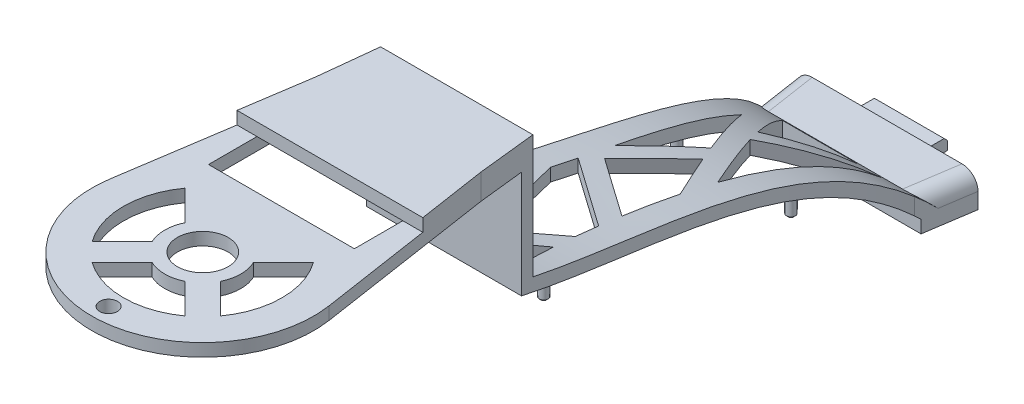
SolidWorks part; units mm, degrees
ref_plane "정면" through (0, 0, 0) normal (0, 0, 1) x (1, 0, 0)
ref_plane "윗면" through (0, 0, 0) normal (0, 1, 0) x (1, 0, 0)
ref_plane "우측면" through (0, 0, 0) normal (1, 0, 0) x (0, 0, -1)
sketch "스케치1" plane through (0, 0, 0) normal (1, 0, 0) x (0, 0, -1)
  line L1 (0, 0) -> (117.6994, 0)
  line L2 (0, 0) -> (0, 39)
  line L3 (0, 39) -> (125.5, 39)
  line L4 (125.5, 0) -> (125.5, 39)
  line L5 (120.5, 0) -> (95.5, 26.9) construction
  line L6 (95.5, 26.9) -> (48.49, 6.9) construction
  line L7 (48.49, 6.9) -> (20.28, 36.9) construction
  line L8 (20.28, 36.9) -> (20.28, 56.9) construction
  line L9 (55.6431, 37) -> (55.6431, -2)
  line L10 (0, -3.1) -> (125.5, -3.1) construction
  line L11 (0, -2) -> (125.5, -2)
  line L12 (0, 37) -> (55.6431, 37)
  line L13 (57.6431, 39) -> (57.6431, -2)
  line L14 (125.5, 0) -> (125.5, -2)
  line L15 (117.6994, 0) -> (117.6994, -2)
  line L16 (120.5, 0) -> (125.5, 0)
  line L17 (0, 0) -> (125.5, 0) construction
  line L18 (55.6431, 39) -> (55.6431, -2) construction
  line L19 (57.6431, 37) -> (125.5, 37)
  line L20 (0, 37) -> (125.5, 37) construction
  spline S0 degree 4 poles (120.5, 0) (95.5, 26.9) (48.49, 6.9) (20.28, 36.9) (20.28, 56.9) knots 0 0 0 0 0 1 1 1 1 1
  spline S1 degree 1 poles (119.035, -1.3615) (18.28, 56.9) knots 0 0 1 1 construction
  spline S2 degree 3 poles (119.035, -1.3615) (118.7108, -1.0127) (118.1523, -0.4358) (117.1322, 0.5491) (115.3881, 2.1024) (112.6944, 4.1207) (109.1843, 6.2121) (104.2498, 8.5701) (97.6622, 10.8405) (86.5016, 13.5333) (71.9342, 16.0164) (55.0254, 19.8159) (40.0095, 25.8104) (30.0498, 33.0505) (24.1324, 39.9432) (20.8302, 45.5049) (19.1097, 50.2945) (18.4017, 54.1131) (18.28, 55.9643) (18.28, 56.9) knots 0 0 0 0 0.010398 0.017329 0.03125 0.0625 0.09375 0.125 0.1875 0.25 0.375 0.5 0.625 0.75 0.8125 0.875 0.9375 0.96875 1 1 1 1 only from (117.6994, 0) to (18.28, 56.9)
  dimension "D1" = 125.5
  dimension "D2" = 39
  dimension "D4" = 5
  dimension "D5" = 30
  dimension "D6" = 10
  dimension "D7" = 40
  dimension "D8" = 20
  dimension "D9" = 30
  dimension "D10" = 47.01
  dimension "D11" = 28.21
  dimension "D12" = 3.1
  dimension "D13" = 2
  dimension "D14" = 2
  dimension "D15" = 2
  dimension "D16" = 2
extrude "보스-돌출3" add sketch "스케치1" along normal blind 35 contours L12 S2 L3 L2 | S2 L12 S0 L3 | S0 L13 L3 L12 L9 | S2 L13 S0 L9 | S2 L15 L11 L14 L16 S0 L13
sketch "스케치3" plane through (0, 0, -125.5) normal (0, 0, -1) x (-1, 0, 0)
  line L0 (0, 0) -> (0, 21.5828) construction
  line L1 (-35, -2) -> (0, -2)
  line L2 (-35, -2) -> (-35, 3)
  line L3 (-35, 3) -> (0, 3)
  line L4 (0, -2) -> (0, 3)
  dimension "D1" = 5
extrude "보스-돌출4" add sketch "스케치3" against normal up to next
sketch "스케치4" plane through (0, 39, 0) normal (0, 1, 0) x (1, 0, 0)
  line L1 (6, 50) -> (29, 50)
  line L2 (6, 50) -> (6, 30)
  line L3 (6, 30) -> (29, 30)
  line L4 (29, 50) -> (29, 30)
  line L5 (0, 0) -> (0, 57.6431) construction
  line L6 (35, 0) -> (35, 57.6431) construction
  line L8 (35, 0) -> (0, 0) construction
  dimension "D1" = 30
  dimension "D2" = 6
  dimension "D3" = 6
  dimension "D4" = 20
extrude "컷-돌출1" cut sketch "스케치4" against normal up to next
sketch "스케치6" plane through (0, 39, 0) normal (0, 1, 0) x (1, 0, 0)
  line L0 (35, 0) -> (35, 57.6431) construction
  line L1 (0, 57.6431) -> (35, 57.6431)
  line L2 (0, 57.6431) -> (0, 37.6431)
  line L3 (0, 37.6431) -> (35, 37.6431)
  line L4 (35, 57.6431) -> (35, 37.6431)
  dimension "D1" = 20
extrude "보스-돌출5" add sketch "스케치6" along normal blind 2
sketch "스케치5" plane through (0, 41, 0) normal (0, 1, 0) x (1, 0, 0)
  line L0 (17.5, 147.5933) -> (17.5, 17.5933) construction
  line L1 (3.5, 147.5933) -> (3.5, 17.5933) construction
  line L2 (31.5, 147.5933) -> (31.5, 17.5933) construction
  line L3 (31.5, 116.6055) -> (35.7897, 144.8117) construction
  line L4 (3.5, 116.6055) -> (-0.7897, 144.8117) construction
  line L5 (3.5, 48.581) -> (-0.7897, 20.3748) construction
  line L6 (31.5, 48.581) -> (35.7897, 20.3748) construction
  line L7 (31.5, 48.581) -> (30.5, 57.5933) construction
  line L8 (30.5, 57.5933) -> (27.5, 82.5933) construction
  line L9 (27.5, 82.5933) -> (27.5, 103.5933) construction
  line L10 (27.5, 103.5933) -> (31.5, 116.6055) construction
  line L11 (3.5, 48.581) -> (4.5, 57.5933) construction
  line L12 (4.5, 57.5933) -> (7.5, 82.5933) construction
  line L13 (7.5, 82.5933) -> (7.5, 103.5933) construction
  line L14 (7.5, 103.5933) -> (3.5, 116.6055) construction
  line L15 (35, 0) -> (35, 37.6431) construction
  line L16 (30.5224, 116.8284) -> (34.8011, 144.9621)
  line L17 (4.4776, 116.8284) -> (0.1989, 144.9621)
  line L18 (4.4917, 48.4507) -> (0.1989, 20.2245)
  line L19 (30.5083, 48.4507) -> (34.8011, 20.2245)
  line L21 (36, -0.9067) -> (-1, -0.9067)
  line L22 (36, -0.9067) -> (36, 166.0933)
  line L23 (36, 166.0933) -> (-1, 166.0933)
  line L24 (-1, -0.9067) -> (-1, 166.0933)
  arc A1 (-0.7897, 20.3748) -> (35.7897, 20.3748) centre (17.5, 17.5933) ccw construction
  arc A2 (35.7897, 144.8117) -> (-0.7897, 144.8117) centre (17.5, 147.5933) ccw construction
  arc A3 (34.8011, 144.9621) -> (0.1989, 144.9621) centre (17.5, 147.5933) ccw
  arc A4 (0.1989, 20.2245) -> (34.8011, 20.2245) centre (17.5, 17.5933) ccw
  spline S0 degree 4 poles (31.5, 48.581) (30.5, 57.5933) (27.5, 82.5933) (27.5, 103.5933) (31.5, 116.6055) knots 0 0 0 0 0 1 1 1 1 1 construction
  spline S1 degree 4 poles (3.5, 48.581) (4.5, 57.5933) (7.5, 82.5933) (7.5, 103.5933) (3.5, 116.6055) knots 0 0 0 0 0 1 1 1 1 1 construction
  spline S4 degree 3 poles (4.4776, 116.8284) (4.6511, 116.2605) (4.9694, 115.134) (5.554, 112.7246) (6.1629, 109.5181) (6.7182, 105.3596) (7.2367, 99.4592) (7.5, 91.5139) (7.3092, 81.4788) (6.8366, 73.1226) (6.3471, 66.7453) (5.9459, 62.2019) (5.5332, 57.9884) (5.1999, 54.8323) (4.9525, 52.5725) (4.7798, 51.0225) (4.6501, 49.8675) (4.5554, 49.023) (4.5133, 48.6452) (4.4917, 48.4507) knots -0.000557 -0.000557 -0.000557 -0.000557 0.030669 0.061895 0.124346 0.186798 0.24925 0.374153 0.499057 0.62396 0.686412 0.748864 0.811316 0.873767 0.904993 0.936219 0.967445 0.983058 0.998671 0.998671 0.998671 0.998671
  spline S5 degree 3 poles (30.5083, 48.4507) (30.4867, 48.6452) (30.4446, 49.023) (30.3499, 49.8675) (30.2202, 51.0225) (30.0475, 52.5725) (29.8001, 54.8323) (29.4668, 57.9884) (29.0541, 62.2019) (28.6529, 66.7453) (28.1634, 73.1226) (27.6908, 81.4788) (27.5, 91.5139) (27.7633, 99.4592) (28.2818, 105.3596) (28.8371, 109.5181) (29.446, 112.7246) (30.0306, 115.134) (30.3489, 116.2605) (30.5224, 116.8284) knots -0.000557 -0.000557 -0.000557 -0.000557 0.015056 0.030669 0.061895 0.09312 0.124346 0.186798 0.24925 0.311702 0.374153 0.499057 0.62396 0.748864 0.811316 0.873767 0.936219 0.967445 0.998671 0.998671 0.998671 0.998671
  dimension "D3" = 37
  dimension "D4" = 18.5
  dimension "D2" = 130
  dimension "D5" = 20
  dimension "D6" = 10
  dimension "D7" = 40
  dimension "D8" = 44
  dimension "D9" = 26
  dimension "D10" = 20
  dimension "D11" = 10
  dimension "D12" = 13
  dimension "D13" = 14
  dimension "D14" = 28
  dimension "D15" = 17.5
extrude "컷-돌출3" cut sketch "스케치5" against normal up to next
sketch "스케치7" plane through (0, 39, 0) normal (0, 1, 0) x (1, 0, 0)
  line L8 (20.0858, 12.1791) -> (24.8108, 7.4541)
  line L9 (12.0858, 15.0075) -> (7.3608, 10.2825)
  line L13 (14.9142, 12.1791) -> (10.1892, 7.4541)
  line L14 (12.0858, 20.1791) -> (7.3608, 24.904)
  line L31 (22.9142, 15.0075) -> (27.6392, 10.2825)
  line L34 (22.9142, 20.1791) -> (27.6392, 24.904)
  arc A1 (10.1892, 7.4541) -> (24.8108, 7.4541) centre (17.5, 17.5933) ccw
  arc A2 (0.1989, 20.2245) -> (34.8011, 20.2245) centre (17.5, 17.5933) ccw construction
  arc A6 (27.6392, 10.2825) -> (27.6392, 24.904) centre (17.5, 17.5933) ccw
  arc A8 (7.3608, 24.904) -> (7.3608, 10.2825) centre (17.5, 17.5933) ccw
  arc A10 (12.0858, 20.1791) -> (12.0858, 15.0075) centre (17.5, 17.5933) ccw
  arc A12 (14.9142, 12.1791) -> (20.0858, 12.1791) centre (17.5, 17.5933) ccw
  arc A13 (22.9142, 15.0075) -> (22.9142, 20.1791) centre (17.5, 17.5933) ccw
  circle A15 centre (17.5, 17.5933) radius 4
  point P18 (17.5, 17.5933)
  dimension "D1" = 8
  dimension "D2" = 5
  dimension "D3" = 12
extrude "컷-돌출4" cut sketch "스케치7" against normal up to next
sketch "스케치8" plane through (0, 39, 0) normal (0, 1, 0) x (1, 0, 0)
  line L0 (16.6915, 104.7325) -> (25.292, 116.8284)
  line L1 (15.042, 107.5897) -> (21.611, 116.8284)
  line L2 (16.6915, 104.7325) -> (23.675, 92.6367)
  line L3 (15.5058, 59.5933) -> (10.7742, 71.6966)
  line L4 (18.054, 61.3146) -> (11.2636, 78.6841)
  line L5 (18.054, 61.3146) -> (24.4866, 69.3588)
  line L6 (9.708, 116.8284) -> (15.042, 107.5897)
  line L7 (10.3479, 109.72) -> (16.9647, 98.2594)
  line L10 (9.708, 116.8284) -> (21.611, 116.8284)
  line L11 (16.9647, 98.2594) -> (11.4055, 88.6307)
  line L12 (18.6967, 95.2594) -> (13.0216, 85.43)
  line L13 (18.6967, 95.2594) -> (23.5814, 86.7989)
  line L15 (20.5188, 59.5933) -> (25.087, 65.3061)
  line L16 (11.3909, 82.9037) -> (24.065, 73.4515)
  line L17 (13.0216, 85.43) -> (23.7984, 77.3928)
  line L18 (4.4776, 116.8284) -> (30.5224, 116.8284) construction
  line L19 (26.3566, 59.5933) -> (20.5188, 59.5933)
  line L20 (15.5058, 59.5933) -> (8.6434, 59.5933)
  line L23 (17.5, 116.8284) -> (17.5, 59.5933) construction
  circle A0 centre (17.5, 17.5933) radius 14.85 construction
  spline S0 degree 3 poles (24.065, 73.4515) (24.0985, 73.0512) (24.1339, 72.6533) (24.2642, 71.2756) (24.369, 70.3088) (24.4866, 69.3588) knots 0.730442 0.730442 0.730442 0.730442 0.75 0.75 0.798601 0.798601 0.798601 0.798601
  spline S1 degree 3 poles (23.5814, 86.7989) (23.5811, 86.6958) (23.5809, 86.5928) (23.5773, 83.8819) (23.6241, 81.311) (23.7513, 78.3336) (23.7738, 77.8619) (23.7984, 77.3928) knots 0.495065 0.495065 0.495065 0.495065 0.5 0.5 0.625 0.625 0.648677 0.648677 0.648677 0.648677
  spline S2 degree 3 poles (11.4055, 88.6307) (11.3837, 90.5396) (11.3369, 92.4621) (11.1766, 97.0255) (11.0443, 99.6656) (10.7282, 104.807) (10.5449, 107.3109) (10.3479, 109.72) knots 0.534087 0.534087 0.534087 0.534087 0.625 0.625 0.75 0.75 0.872917 0.872917 0.872917 0.872917
  spline S3 degree 3 poles (25.292, 116.8284) (25.0777, 114.6366) (24.8629, 112.2889) (24.4613, 107.3958) (24.2745, 104.8502) (23.9557, 99.6656) (23.8234, 97.0255) (23.7101, 93.8013) (23.6916, 93.2188) (23.675, 92.6367) knots 0 0 0 0 0.125 0.125 0.25 0.25 0.375 0.375 0.402553 0.402553 0.402553 0.402553
  spline S4 degree 3 poles (8.6434, 59.5933) (9.1018, 61.2446) (9.4912, 62.9805) (10.2116, 66.9347) (10.5195, 69.1849) (10.7628, 71.5836) (10.7685, 71.6401) (10.7742, 71.6966) knots 0.019059 0.019059 0.019059 0.019059 0.125 0.125 0.25 0.25 0.253012 0.253012 0.253012 0.253012
  spline S5 degree 3 poles (25.087, 65.3061) (25.117, 65.1348) (25.1474, 64.9643) (25.5088, 62.9805) (25.8982, 61.2446) (26.3566, 59.5933) knots 0.86508 0.86508 0.86508 0.86508 0.875 0.875 0.980941 0.980941 0.980941 0.980941
  spline S6 degree 3 poles (11.2636, 78.6841) (11.2654, 78.7253) (11.3253, 80.1132) (11.3666, 81.522) (11.3909, 82.9037) knots 0.372941 0.372941 0.372941 0.372941 0.375 0.442278 0.442278 0.442278 0.442278
  dimension "D1" = 60
  dimension "D2" = 120
  dimension "D4" = 60
extrude "컷-돌출5" cut sketch "스케치8" against normal up to next
fillet "필렛1" radius 2.5 2 edges
sketch "스케치9" plane through (0, 0, -125.5) normal (0, 0, -1) x (-1, 0, 0)
  line L1 (-23, -0.35) -> (-12, -0.35)
  line L2 (-23, -0.35) -> (-23, 1.55)
  line L3 (-23, 1.55) -> (-12, 1.55)
  line L4 (-12, -0.35) -> (-12, 1.55)
  line L5 (-23, -0.35) -> (-12, 1.55) construction
  line L6 (-23, 1.55) -> (-12, -0.35) construction
  line L8 (-31.8412, -2) -> (-3.1588, -2) construction
  point P4 (-17.5, 0.6)
  point P7 (-17.5, -2)
  dimension "D1" = 1.9
  dimension "D2" = 11
  dimension "D3" = 5.5
  dimension "D4" = 1.65
extrude "보스-돌출6" add sketch "스케치9" along normal blind 4
chamfer "모따기1" distance 0.5 angle 45 1 edges at (17.5, 1.55, -129.5)
sketch "스케치10" plane through (0, -2, 0) normal (0, -1, 0) x (1, 0, 0)
  line L0 (7.5, -61.3494) -> (27.5, -61.3494) construction
  line L1 (8.5, -101.3494) -> (26.5, -101.3494) construction
  line L2 (30.6549, -117.6994) -> (4.3451, -117.6994) construction
  line L3 (17.5, -55.6431) -> (17.5, -117.6994) construction
  line L4 (29.7155, -55.6431) -> (5.2845, -55.6431) construction
  circle A0 centre (7.5, -61.3494) radius 0.7
  circle A1 centre (27.5, -61.3494) radius 0.7
  circle A2 centre (8.5, -101.3494) radius 0.7
  circle A3 centre (26.5, -101.3494) radius 0.7
  dimension "D1" = 1.4
  dimension "D7" = 10
  dimension "D2" = 18
  dimension "D3" = 20
  dimension "D4" = 16.35
  dimension "D5" = 40
  dimension "D6" = 9
extrude "보스-돌출7" add sketch "스케치10" against normal up to next
sketch "스케치11" plane through (0, 0, 0) normal (1, 0, 0) x (0, 0, -1)
  line L0 (62.0494, 15.7634) -> (60.6494, 15.7634)
  line L1 (62.0494, -2) -> (62.0494, 18.3377) construction
  line L2 (60.6494, 18.6909) -> (60.6494, -2) construction
  line L3 (60.6494, 15.7634) -> (60.6494, -2)
  line L4 (60.6494, -2) -> (62.0494, -2)
  line L5 (62.0494, -2) -> (62.0494, 15.7634)
  line L7 (102.0494, -2) -> (100.6494, -2)
  line L11 (102.0494, -2) -> (102.0494, 6.6139)
  line L12 (102.0494, -2) -> (102.0494, 9.2779) construction
  line L14 (102.0494, 6.6139) -> (100.6494, 6.6139)
  line L15 (100.6494, 9.7647) -> (100.6494, -2) construction
  line L16 (100.6494, 6.6139) -> (100.6494, -2)
  spline S2 degree 3 poles (-489.1997, -3954.2079) (94.7461, -322.0323) (184.7254, -40.6683) (107.1293, 4.4747) (104.8927, 5.5161) (100.1948, 7.3342) (97.7342, 8.1098) (92.6497, 9.4874) (90.0258, 10.0891) (82.0137, 11.7696) (76.4885, 12.7168) (-61.3315, 40.1247) (-159.8746, 145.9743) (2327.4223, 3293.6766) knots -4.359543 -4.359543 -4.359543 -4.359543 0.125 0.125 0.25 0.25 0.375 0.375 0.5 0.5 0.75 0.75 6.785445 6.785445 6.785445 6.785445 only from (115.1534, -1.0428) to (54.917, 17.6973)
  spline S3 degree 3 poles (115.1534, -1.0428) (113.3134, 0.6177) (111.3378, 2.0264) (107.1293, 4.4747) (104.8927, 5.5161) (100.1948, 7.3342) (97.7342, 8.1098) (92.6497, 9.4874) (90.0258, 10.0891) (82.0137, 11.7696) (76.4885, 12.7168) (65.525, 14.8971) (60.1013, 16.1237) (54.917, 17.6973) knots 0 0 0 0 0.125 0.125 0.25 0.25 0.375 0.375 0.5 0.5 0.75 0.75 1 1 1 1 construction
  dimension "D1" = 2.5
extrude "컷-돌출6" cut sketch "스케치11" along normal through all
chamfer "모따기2" distance 0.3 angle 45 4 edges at (8.5, 6.6139, -102.0494) (26.5, 6.6139, -102.0494) (7.5, 15.7634, -62.0494) (27.5, 15.7634, -62.0494)
sketch "스케치12" plane through (0, 39, 0) normal (0, 1, 0) x (1, 0, 0)
  line L0 (17.5, 21.5933) -> (17.5, 0.0933) construction
  circle A0 centre (17.5, 2.7433) radius 1.4
  arc A2 (0.1989, 20.2245) -> (34.8011, 20.2245) centre (17.5, 17.5933) ccw construction
  circle A3 centre (17.5, 17.5933) radius 4 construction
  point P2 (0, 0)
  dimension "D1" = 2.8
  dimension "D2" = 14.85
extrude "컷-돌출7" cut sketch "스케치12" against normal up to next
